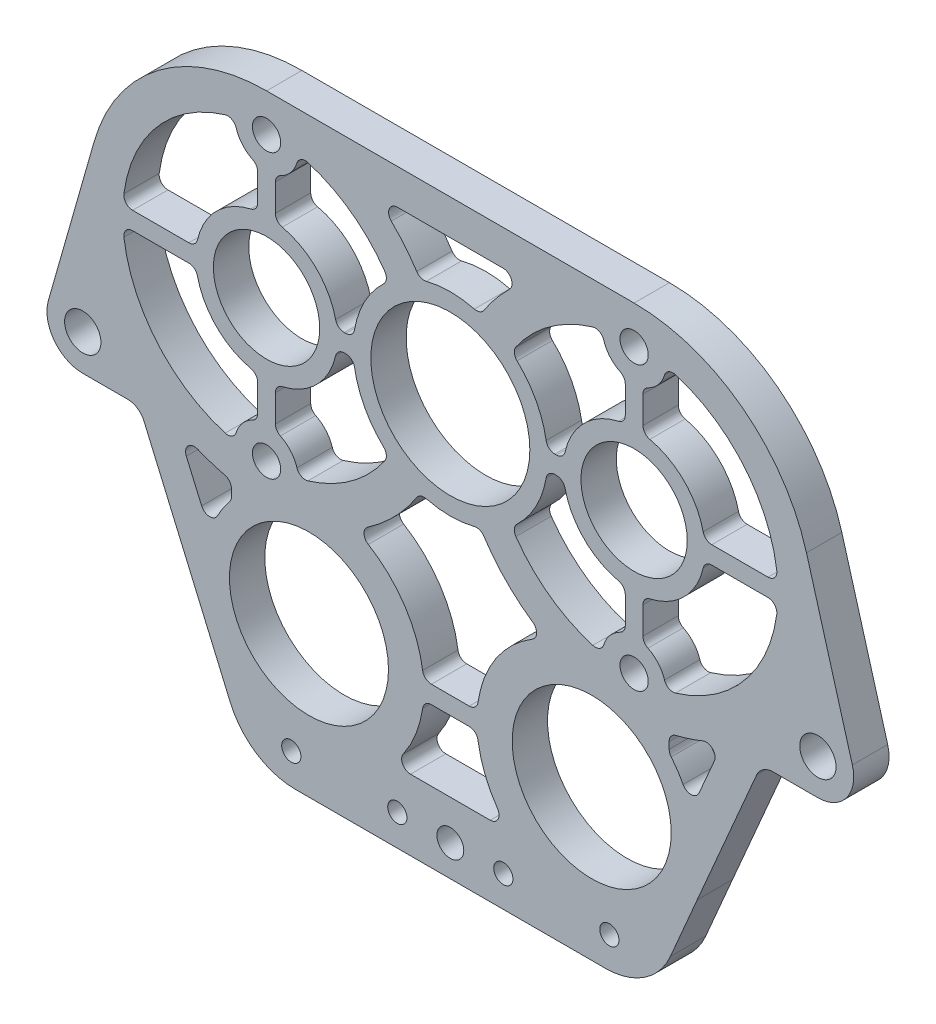
SolidWorks part; units mm, degrees
material "6061 Alloy"
ref_plane "Front Plane" through (0, 0, 0) normal (0, 0, 1) x (1, 0, 0)
ref_plane "Top Plane" through (0, 0, 0) normal (0, 1, 0) x (1, 0, 0)
ref_plane "Right Plane" through (0, 0, 0) normal (1, 0, 0) x (0, 0, -1)
sketch "Sketch1" plane through (0, 0, 0) normal (0, 0, 1) x (1, 0, 0)
  line L0 (-88.7296, -57.0475) -> (-96.9696, -85.9369)
  line L1 (-70.3836, -64.2939) -> (-83.566, -64.2939)
  line L2 (-59.3451, -45.9715) -> (-59.3451, -53.2554)
  line L3 (-59.3451, -85.7913) -> (-59.3451, -78.5074)
  line L4 (-56.1701, -45.9715) -> (-56.1701, -53.2554)
  line L5 (-45.1316, -64.2939) -> (-42.1278, -64.2939)
  line L6 (-56.1701, -85.7913) -> (-56.1701, -78.5074)
  line L7 (-70.3836, -67.4689) -> (-83.566, -67.4689)
  line L8 (-73.8894, -93.7574) -> (-67.9201, -107.5525)
  line L9 (-45.1316, -67.4689) -> (-42.1278, -67.4689)
  line L10 (-64.0572, -97.4665) -> (-64.0572, -100.5443)
  line L11 (-69.0893, -120.875) -> (-60.9774, -139.773)
  line L13 (-29.5612, -111.198) -> (-19.9139, -111.198)
  line L14 (-14.2297, -127.073) -> (-35.2455, -127.073)
  line L15 (-29.5612, -114.373) -> (-19.9139, -114.373)
  line L16 (-57.7576, -33.6742) -> (8.2824, -33.6742)
  line L17 (-10.9194, -40.0242) -> (-38.5558, -40.0242)
  line L18 (30.2994, -96.0869) -> (19.6141, -120.875)
  line L19 (-4.3436, -67.4689) -> (-7.3474, -67.4689)
  line L20 (41.3024, -94.1419) -> (33.2559, -94.1419)
  line L21 (20.9084, -67.4689) -> (34.0908, -67.4689)
  line L22 (6.6949, -85.7913) -> (6.6949, -78.5074)
  line L23 (-4.3436, -64.2939) -> (-7.3474, -64.2939)
  line L24 (6.6949, -45.9715) -> (6.6949, -53.2554)
  line L25 (9.8699, -85.7913) -> (9.8699, -78.5074)
  line L26 (9.8699, -45.9715) -> (9.8699, -53.2554)
  line L27 (20.9084, -64.2939) -> (34.0908, -64.2939)
  line L28 (39.2544, -57.0475) -> (47.4944, -85.9369)
  line L29 (-90.7776, -94.1419) -> (-82.7311, -94.1419)
  line L30 (-79.7746, -96.0869) -> (-69.0893, -120.875)
  line L31 (-60.9774, -139.773) -> (11.5022, -139.773)
  line L32 (19.6141, -120.875) -> (11.5022, -139.773)
  line L33 (24.4142, -93.7574) -> (18.4449, -107.5525)
  line L40 (14.582, -97.4665) -> (14.582, -100.5443)
  circle A0 centre (-57.7576, -65.8814) radius 9.5504
  circle A1 centre (-57.7576, -40.4814) radius 2.54
  arc A2 (-41.8493, -93.8855) -> (-30.1579, -82.4814) centre (-57.7576, -65.8814) ccw
  circle A3 centre (-57.7576, -91.2814) radius 2.54
  circle A4 centre (-90.7776, -87.703) radius 3.2639
  arc A5 (-52.0455, -91.0998) -> (-56.1701, -85.7913) centre (-57.7576, -91.2814) ccw
  arc A6 (-52.0455, -91.0998) -> (-35.741, -79.4411) centre (-57.7576, -65.8814) ccw
  arc A7 (-52.0455, -40.663) -> (-56.1701, -45.9715) centre (-57.7576, -40.4814) cw
  arc A8 (-59.3451, -45.9715) -> (-63.4697, -40.663) centre (-57.7576, -40.4814) cw
  arc A9 (-56.1701, -78.5074) -> (-45.1316, -67.4689) centre (-57.7576, -65.8814) ccw
  arc A10 (-59.3451, -85.7913) -> (-63.4697, -91.0998) centre (-57.7576, -91.2814) ccw
  arc A11 (-83.566, -67.4689) -> (-63.4697, -91.0998) centre (-57.7576, -65.8814) ccw
  arc A12 (-59.3451, -53.2554) -> (-70.3836, -64.2939) centre (-57.7576, -65.8814) ccw
  circle A13 centre (-50.1376, -112.7855) radius 14.2875
  arc A14 (-70.3836, -67.4689) -> (-59.3451, -78.5074) centre (-57.7576, -65.8814) ccw
  arc A15 (-45.1316, -64.2939) -> (-56.1701, -53.2554) centre (-57.7576, -65.8814) ccw
  arc A16 (-63.4697, -40.663) -> (-83.566, -64.2939) centre (-57.7576, -65.8814) ccw
  arc A17 (-30.1579, -82.4814) -> (-19.3173, -82.4814) centre (-24.7376, -65.8814) ccw
  arc A18 (-64.0572, -100.5443) -> (-67.9201, -107.5525) centre (-50.1376, -112.7855) ccw
  arc A19 (39.1749, -56.7733) -> (39.2544, -57.0475) centre (8.2824, -65.8814) cw
  circle A20 centre (-24.7376, -65.8814) radius 14.2875
  arc A21 (-35.741, -52.3218) -> (-42.1278, -64.2939) centre (-24.7376, -65.8814) ccw
  arc A22 (-35.741, -52.3218) -> (-52.0455, -40.663) centre (-57.7576, -65.8814) ccw
  arc A23 (-42.1278, -67.4689) -> (-35.741, -79.4411) centre (-24.7376, -65.8814) ccw
  arc A24 (-30.1579, -49.2814) -> (-38.5558, -40.0242) centre (-57.7576, -65.8814) ccw
  arc A25 (-19.3173, -49.2814) -> (-30.1579, -49.2814) centre (-24.7376, -65.8814) ccw
  arc A26 (-29.5612, -111.198) -> (-41.8493, -93.8855) centre (-50.1376, -112.7855) ccw
  arc A27 (-35.2455, -127.073) -> (-29.5612, -114.373) centre (-50.1376, -112.7855) ccw
  arc A28 (-57.7576, -33.6742) -> (-88.6501, -56.7733) centre (-57.7576, -65.8814) ccw
  arc A29 (8.2824, -33.6742) -> (39.1749, -56.7733) centre (8.2824, -65.8814) cw
  arc A30 (-14.2297, -127.073) -> (-19.9139, -114.373) centre (0.6624, -112.7855) cw
  arc A31 (-19.9139, -111.198) -> (-7.6259, -93.8855) centre (0.6624, -112.7855) cw
  arc A32 (-19.3173, -49.2814) -> (-10.9194, -40.0242) centre (8.2824, -65.8814) cw
  arc A33 (-7.3474, -67.4689) -> (-13.7342, -79.4411) centre (-24.7376, -65.8814) cw
  arc A34 (-13.7342, -52.3218) -> (2.5703, -40.663) centre (8.2824, -65.8814) cw
  arc A35 (-13.7342, -52.3218) -> (-7.3474, -64.2939) centre (-24.7376, -65.8814) cw
  arc A36 (30.2994, -96.0869) -> (33.2559, -94.1419) centre (33.2559, -97.3614) cw
  arc A37 (47.4944, -85.9369) -> (41.3024, -94.1419) centre (41.3024, -87.703) cw
  arc A38 (13.9945, -40.663) -> (34.0908, -64.2939) centre (8.2824, -65.8814) cw
  arc A39 (-4.3436, -64.2939) -> (6.6949, -53.2554) centre (8.2824, -65.8814) cw
  arc A40 (20.9084, -67.4689) -> (9.8699, -78.5074) centre (8.2824, -65.8814) cw
  circle A41 centre (0.6624, -112.7855) radius 14.2875
  arc A42 (9.8699, -53.2554) -> (20.9084, -64.2939) centre (8.2824, -65.8814) cw
  arc A43 (34.0908, -67.4689) -> (13.9945, -91.0998) centre (8.2824, -65.8814) cw
  arc A44 (9.8699, -85.7913) -> (13.9945, -91.0998) centre (8.2824, -91.2814) cw
  arc A45 (6.6949, -78.5074) -> (-4.3436, -67.4689) centre (8.2824, -65.8814) cw
  arc A46 (9.8699, -45.9715) -> (13.9945, -40.663) centre (8.2824, -40.4814) ccw
  arc A47 (2.5703, -40.663) -> (6.6949, -45.9715) centre (8.2824, -40.4814) ccw
  arc A48 (2.5703, -91.0998) -> (-13.7342, -79.4411) centre (8.2824, -65.8814) cw
  arc A49 (2.5703, -91.0998) -> (6.6949, -85.7913) centre (8.2824, -91.2814) cw
  arc A50 (-96.9696, -85.9369) -> (-90.7776, -94.1419) centre (-90.7776, -87.703) ccw
  circle A51 centre (8.2824, -91.2814) radius 2.54
  arc A52 (-7.6259, -93.8855) -> (-19.3173, -82.4814) centre (8.2824, -65.8814) cw
  circle A53 centre (8.2824, -40.4814) radius 2.54
  circle A54 centre (8.2824, -65.8814) radius 9.5504
  circle A55 centre (-53.3126, -134.185) radius 1.7272
  circle A56 centre (-24.7376, -134.185) radius 2.413
  circle A57 centre (-34.2626, -134.185) radius 1.7272
  circle A58 centre (-15.2126, -134.185) radius 1.7272
  circle A59 centre (3.8374, -134.185) radius 1.7272
  arc A60 (-79.7746, -96.0869) -> (-82.7311, -94.1419) centre (-82.7311, -97.3614) ccw
  circle A61 centre (41.3024, -87.703) radius 3.2639
  arc A62 (14.582, -100.5443) -> (18.4449, -107.5525) centre (0.6624, -112.7855) cw
  arc A63 (24.4142, -93.7574) -> (14.582, -97.4665) centre (8.2824, -65.8814) cw
  arc A65 (-88.6501, -56.7733) -> (-88.7296, -57.0475) centre (-57.7576, -65.8814) ccw
  arc A66 (-73.8894, -93.7574) -> (-64.0572, -97.4665) centre (-57.7576, -65.8814) ccw
  point P3 (-24.7376, -65.8814)
  point P48 (-24.7376, -127.073)
  point P51 (-24.7376, -111.198)
  point P54 (-24.7376, -111.198)
  point P57 (-24.7376, -114.373)
  point P58 (-24.7376, -33.6742)
  point P104 (-24.7376, -40.0242)
  point P109 (-60.9774, -139.773)
  point P113 (11.5022, -139.773)
  dimension "D2" = 19.1008
  dimension "D4" = 5.08
  dimension "D8" = 25.4
  dimension "D9" = 3.175
  dimension "D10" = 11.43
  dimension "D11" = 33.02
  dimension "D12" = 46.9041
  dimension "D13" = 25.4
  dimension "D14" = 6.5278
  dimension "D15" = 1.5875
  dimension "D17" = 5.715
  dimension "D18" = 28.575
  dimension "D23" = 1.5875
  dimension "D27" = 6.4389
  dimension "D7" = 64.4144
  dimension "D28" = 34.925
  dimension "D29" = 25.4508
  dimension "D30" = 51.7144
  dimension "D5" = 5.08
  dimension "D16" = 5.715
  dimension "D24" = 3.4544
  dimension "D25" = 28.575
  dimension "D26" = 3.2195
  dimension "D36" = 3.4544
  dimension "D37" = 4.826
  dimension "D40" = 19.05
  dimension "D41" = 32.2072
  dimension "D42" = 9.525
  dimension "D6" = 25.4
  dimension "D19" = 3.175
  dimension "D20" = 1.5875
  dimension "D31" = 3.175
  dimension "D21" = 33.02
  dimension "D22" = 3.175
  dimension "D32" = 1.5875
  dimension "D33" = 28.2605
  dimension "D34" = 6.35
  dimension "D35" = 26.9875
  dimension "D38" = 5.588
  dimension "D39" = 0
  dimension "D43" = 5.588
  dimension "D44" = 5.588
  dimension "D45" = 66.04
extrude "Boss-Extrude1" add sketch "Sketch1" along normal blind 6.35 contours A0 region at (-86.9649, -57.4107, 0)
fillet "Fillet1" radius 12.7 2 edges at (-60.9774, -139.773, 3.175) (11.5022, -139.773, 3.175)
fillet "Fillet2" radius 1.5875 22 edges at (-63.4697, -91.0998, 3.175) (-59.3451, -85.7913, 3.175) (-52.0455, -91.0998, 3.175) (-56.1701, -85.7913, 3.175) (-35.741, -79.4411, 3.175) (-59.3451, -78.5074, 3.175) (-56.1701, -78.5074, 3.175) (-45.1316, -67.4689, 3.175) (-42.1278, -67.4689, 3.175) (-59.3451, -45.9715, 3.175) (-45.1316, -64.2939, 3.175) (-42.1278, -64.2939, 3.175) (-35.741, -52.3218, 3.175) (-56.1701, -45.9715, 3.175) (-56.1701, -53.2554, 3.175) (-59.3451, -53.2554, 3.175) (-70.3836, -64.2939, 3.175) (-70.3836, -67.4689, 3.175) (-83.566, -67.4689, 3.175) (-83.566, -64.2939, 3.175) (-52.0455, -40.663, 3.175) (-63.4697, -40.663, 3.175)
fillet "Fillet3" radius 1.5875 22 edges at (13.9945, -91.0998, 3.175) (9.8699, -85.7913, 3.175) (2.5703, -91.0998, 3.175) (6.6949, -85.7913, 3.175) (-13.7342, -79.4411, 3.175) (9.8699, -78.5074, 3.175) (-7.3474, -67.4689, 3.175) (-4.3436, -67.4689, 3.175) (6.6949, -78.5074, 3.175) (34.0908, -67.4689, 3.175) (20.9084, -67.4689, 3.175) (34.0908, -64.2939, 3.175) (9.8699, -45.9715, 3.175) (13.9945, -40.663, 3.175) (20.9084, -64.2939, 3.175) (9.8699, -53.2554, 3.175) (-7.3474, -64.2939, 3.175) (-4.3436, -64.2939, 3.175) (6.6949, -53.2554, 3.175) (-13.7342, -52.3218, 3.175) (6.6949, -45.9715, 3.175) (2.5703, -40.663, 3.175)
fillet "Fillet4" radius 1.5875 14 edges at (-35.2455, -127.073, 3.175) (-14.2297, -127.073, 3.175) (-19.9139, -114.373, 3.175) (-29.5612, -114.373, 3.175) (-29.5612, -111.198, 3.175) (-19.9139, -111.198, 3.175) (-7.6259, -93.8855, 3.175) (-41.8493, -93.8855, 3.175) (-19.3173, -82.4814, 3.175) (-30.1579, -82.4814, 3.175) (-19.3173, -49.2814, 3.175) (-30.1579, -49.2814, 3.175) (-10.9194, -40.0242, 3.175) (-38.5558, -40.0242, 3.175)
fillet "Fillet5" radius 1.5875 8 edges at (24.4142, -93.7574, 3.175) (18.4449, -107.5525, 3.175) (14.582, -100.5443, 3.175) (14.582, -97.4665, 3.175) (-73.8894, -93.7574, 3.175) (-64.0572, -97.4665, 3.175) (-67.9201, -107.5525, 3.175) (-64.0572, -100.5443, 3.175)
